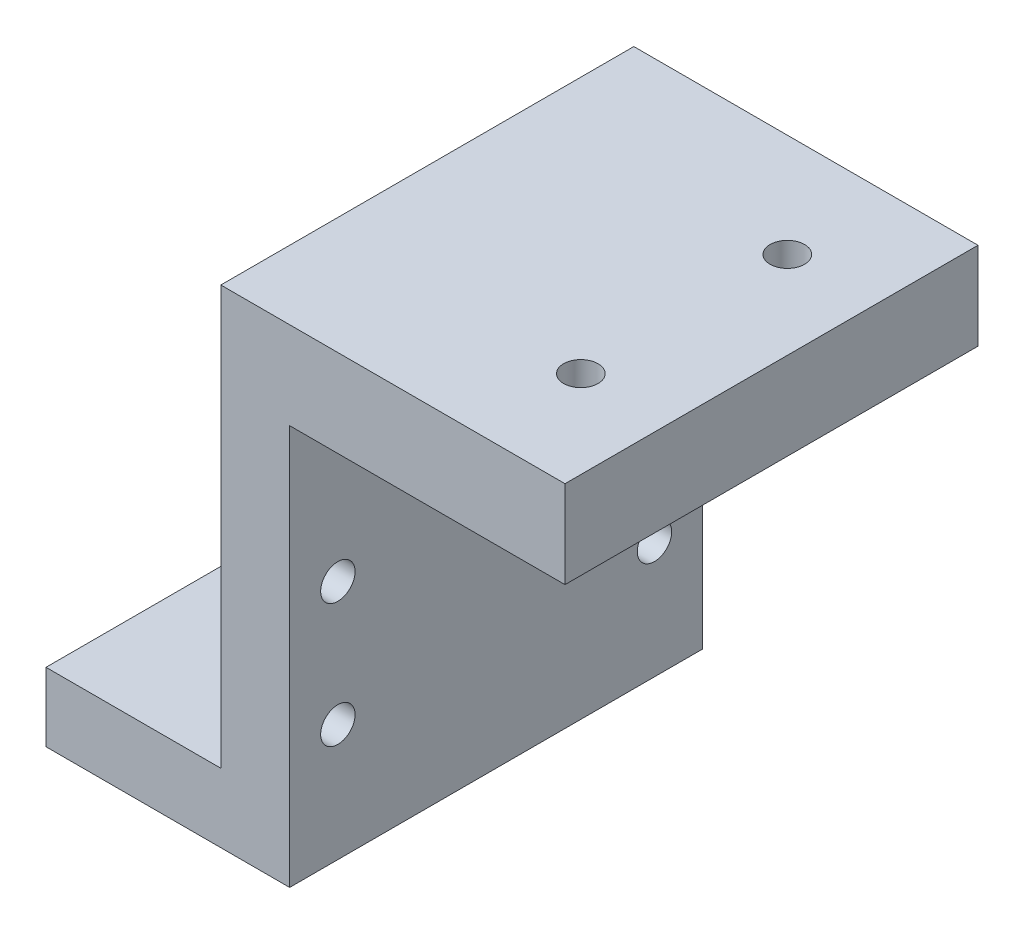
SolidWorks part; units mm, degrees
material "ABS"
ref_plane "Front Plane" through (0, 0, 0) normal (0, 0, 1) x (1, 0, 0)
ref_plane "Top Plane" through (0, 0, 0) normal (0, 1, 0) x (1, 0, 0)
ref_plane "Right Plane" through (0, 0, 0) normal (1, 0, 0) x (0, 0, -1)
sketch "Sketch1" plane through (0, 0, 0) normal (0, 0, 1) x (1, 0, 0)
  line L1 (-25, -6.35) -> (25, -6.35)
  line L2 (-25, -6.35) -> (-25, 6.35)
  line L3 (-25, 6.35) -> (25, 6.35)
  line L4 (25, -6.35) -> (25, 6.35)
  line L5 (-25, -6.35) -> (25, 6.35) construction
  line L6 (-25, 6.35) -> (25, -6.35) construction
  point P0 (0, 0)
  dimension "D1" = 12.7
  dimension "D2" = 50
extrude "Boss-Extrude1" add sketch "Sketch1" along normal blind 60
sketch "Sketch2" plane through (0, -6.35, 0) normal (0, -1, 0) x (1, 0, 0)
  line L0 (-25, 0) -> (25, 0) construction
  line L1 (-25, 60) -> (-15, 60)
  line L2 (-25, 60) -> (-25, 0)
  line L3 (-25, 0) -> (-15, 0)
  line L4 (-15, 60) -> (-15, 0)
  dimension "D1" = 10
extrude "Boss-Extrude2" add sketch "Sketch2" along normal blind 58.1
sketch "Sketch3" plane through (-25, 0, 0) normal (-1, 0, 0) x (0, 0, 1)
  line L0 (60, 6.35) -> (60, -64.45) construction
  line L1 (0, -64.45) -> (60, -64.45)
  line L2 (0, -64.45) -> (0, -54.45)
  line L3 (0, -54.45) -> (60, -54.45)
  line L4 (60, -64.45) -> (60, -54.45)
  dimension "D1" = 10
extrude "Boss-Extrude3" add sketch "Sketch3" along normal blind 25.4
sketch "Sketch4" plane through (0, 6.35, 0) normal (0, 1, 0) x (1, 0, 0)
  line L0 (25, -60) -> (-25, -60) construction
  line L1 (25, 0) -> (-0.4, 0)
  line L2 (25, 0) -> (25, -60)
  line L3 (25, -60) -> (-0.4, -60)
  line L4 (-0.4, 0) -> (-0.4, -60)
  line L5 (-0.4, -60) -> (25, 0) construction
  line L6 (12.3, -30) -> (12.3, 0) construction
  line L7 (12.3, -30) -> (12.3, -60) construction
  point P9 (12.3, -15)
  point P11 (12.3, -45)
  point P13 (12.3, -15)
  point P15 (12.3, -45)
  dimension "D1" = 25.4
sketch "Sketch7" plane through (-15, 0, 0) normal (1, 0, 0) x (0, 0, -1)
  line L0 (-60, -64.45) -> (-60, -6.35) construction
  line L1 (0, -6.35) -> (-60, -6.35)
  line L2 (0, -6.35) -> (0, -64.45)
  line L3 (0, -64.45) -> (-60, -64.45)
  line L4 (-60, -6.35) -> (-60, -64.45)
  line L8 (-30, -6.35) -> (-30, -64.45) construction
  line L11 (0, -64.45) -> (-60, -64.45) construction
  point P28 (-53, -47.45)
  point P31 (-7, -47.45)
  point P35 (-53, -29.45)
  point P37 (-7, -29.45)
  dimension "D3" = 35
  dimension "D2" = 46
  dimension "D1" = 18
hole_wizard "M5x0.8 Tapped Hole1" positions "Sketch4" profile "Sketch8" tap size "M5x0.8" standard "ANSI Metric" end condition through all
sketch "Sketch8" plane through (12.3, 6.35, 45) normal (1, 0, 0) x (0, 0, 1)
  line L0 (0, 0) -> (0, 70.8)
  line L1 (0, 70.8) -> (2.5, 70.8)
  line L2 (2.5, 70.8) -> (2.5, 0)
  line L5 (2.5, 0) -> (0, 0)
  line L11 (0, -6.35) -> (0, 107.95) construction
  dimension "Thread Major Dia." = 5
  dimension "Thru Tap Drill Depth" = 70.8
hole_wizard "M5x0.8 Tapped Hole2" positions "Sketch7" profile "Sketch9" tap size "M5x0.8" standard "ANSI Metric" end condition through all
sketch "Sketch9" plane through (-15, -29.45, 7) normal (0, 1, 0) x (0, 0, -1)
  line L0 (0, 0) -> (0, 35.4)
  line L1 (0, 35.4) -> (2.5, 35.4)
  line L2 (2.5, 35.4) -> (2.5, 0)
  line L5 (2.5, 0) -> (0, 0)
  line L11 (0, -6.35) -> (0, 107.95) construction
  dimension "Thread Major Dia." = 5
  dimension "Thru Tap Drill Depth" = 35.4
